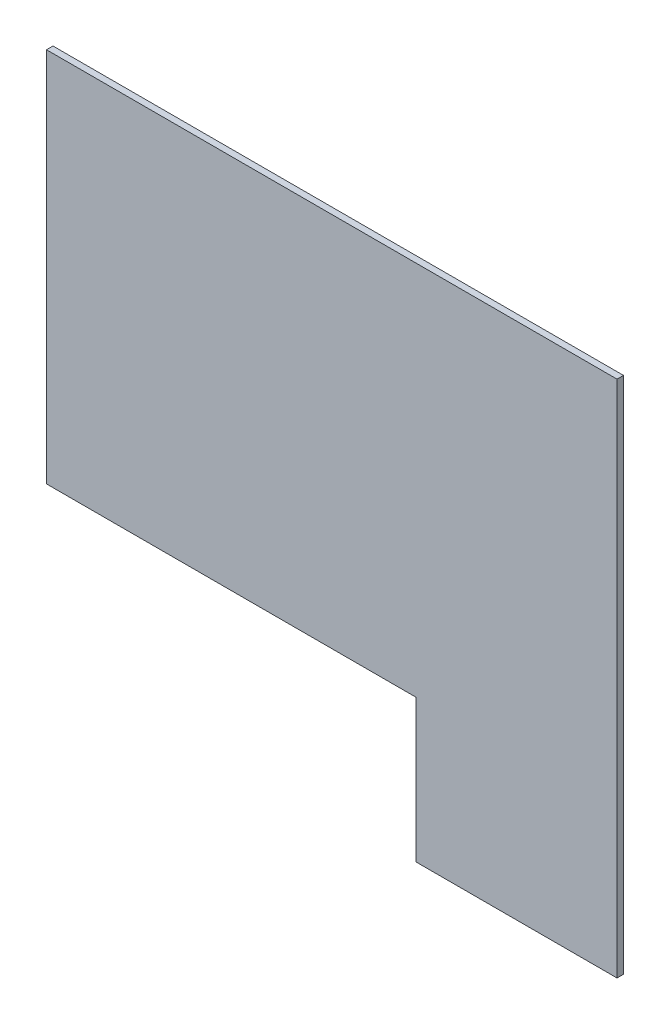
SolidWorks part; units mm, degrees
ref_plane "Alzado" through (0, 0, 0) normal (0, 0, 1) x (1, 0, 0)
ref_plane "Planta" through (0, 0, 0) normal (0, 1, 0) x (1, 0, 0)
ref_plane "Vista lateral" through (0, 0, 0) normal (1, 0, 0) x (0, 0, -1)
sketch "Croquis1" plane through (0, 0, 0) normal (0, 0, 1) x (-1, 0, 0)
  line L19 (-143.5867, 402.2958) -> (-228.5867, 402.2958)
  line L22 (-228.5867, 2.2958) -> (-228.5867, 402.2958)
  line L24 (211.4133, 2.2958) -> (211.4133, 292.2958)
  line L26 (-228.5867, 2.2958) -> (211.4133, 2.2958)
  line L27 (211.4133, 292.2958) -> (-73.5867, 292.2958)
  line L28 (-143.5867, 402.2958) -> (-73.5867, 402.2958)
  line L31 (-73.5867, 402.2958) -> (-73.5867, 292.2958)
  point P10 (0, 0)
  dimension "D1" = 400
  dimension "D2" = 440
  dimension "D3" = 85
  dimension "D4" = 290
  dimension "D5" = 70
extrude "Saliente-Extruir1" add sketch "Croquis1" along normal blind 5
